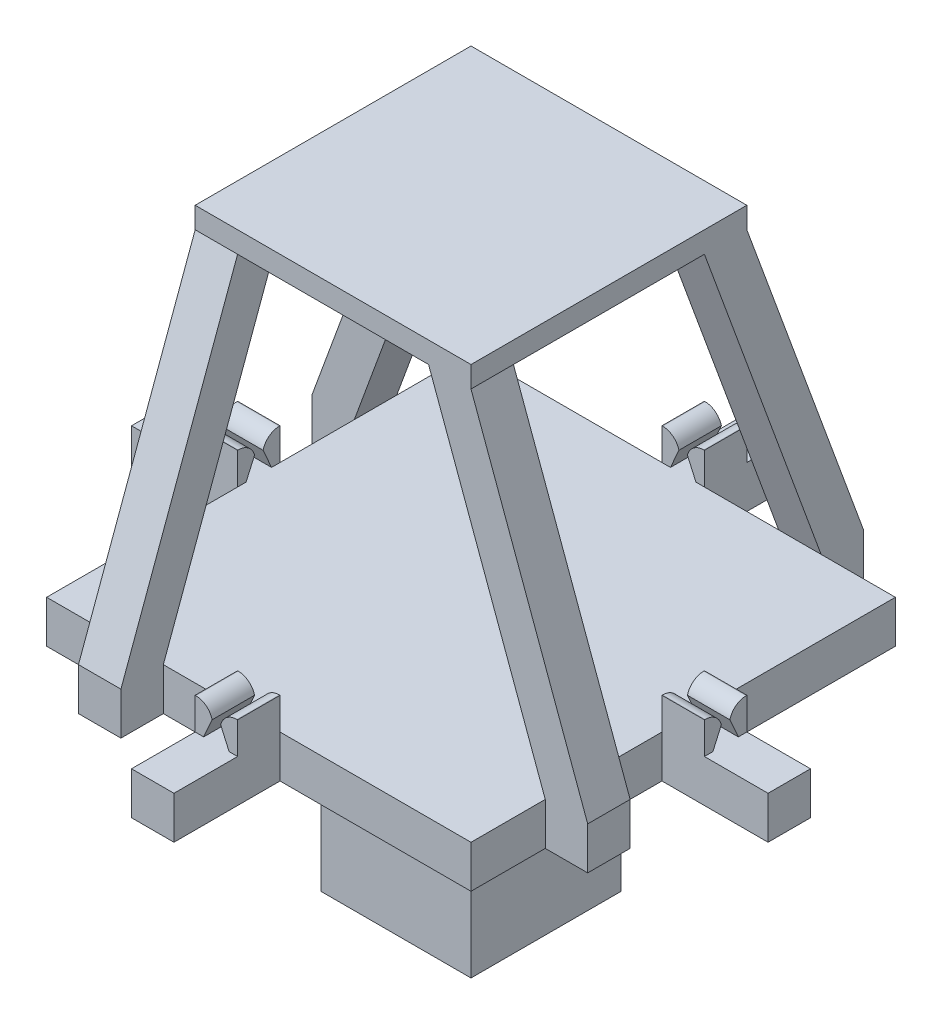
SolidWorks part; units mm, degrees
ref_plane "Front Plane" through (0, 0, 0) normal (0, 0, 1) x (1, 0, 0)
ref_plane "Top Plane" through (0, 0, 0) normal (0, 1, 0) x (1, 0, 0)
ref_plane "Right Plane" through (0, 0, 0) normal (1, 0, 0) x (0, 0, -1)
sketch "Sketch2" plane through (0, 0, 0) normal (0, 1, 0) x (1, 0, 0)
  line L1 (-50, -50) -> (50, -50)
  line L2 (-50, -50) -> (-50, 50)
  line L3 (-50, 50) -> (50, 50)
  line L4 (50, -50) -> (50, 50)
  line L5 (-50, -50) -> (50, 50) construction
  line L6 (-50, 50) -> (50, -50) construction
  point P0 (0, 0)
extrude "Boss-Extrude1" add sketch "Sketch2" along normal blind 5
sketch "Sketch3" plane through (0, 0, 0) normal (0, -1, 0) x (1, 0, 0)
  line L1 (-50, -50) -> (50, -50)
  line L2 (-50, -50) -> (-50, 50)
  line L3 (-50, 50) -> (50, 50)
  line L4 (50, -50) -> (50, 50)
  line L5 (-50, -50) -> (50, 50) construction
  line L6 (-50, 50) -> (50, -50) construction
  point P0 (0, 0)
extrude "Boss-Extrude2" add sketch "Sketch3" along normal blind 5
sketch "Sketch8" plane through (0, -5, 0) normal (0, -1, 0) x (1, 0, 0)
  circle A0 centre (0, 0) radius 5
extrude "Boss-Extrude7" add sketch "Sketch8" along normal blind 30
sketch "Sketch9" plane through (0, -35, 0) normal (0, -1, 0) x (1, 0, 0)
  line L1 (-17.7, 17.7) -> (17.7, 17.7)
  line L2 (-17.7, 17.7) -> (-17.7, -17.7)
  line L3 (-17.7, -17.7) -> (17.7, -17.7)
  line L4 (17.7, 17.7) -> (17.7, -17.7)
  line L5 (-17.7, 17.7) -> (17.7, -17.7) construction
  line L6 (-17.7, -17.7) -> (17.7, 17.7) construction
  point P0 (0, 0)
extrude "Boss-Extrude8" add sketch "Sketch9" along normal blind 20
sketch "Sketch10" plane through (0, -55, 0) normal (0, -1, 0) x (1, 0, 0)
  line L1 (-12.7, 12.7) -> (12.7, 12.7)
  line L2 (-12.7, 12.7) -> (-12.7, -12.7)
  line L3 (-12.7, -12.7) -> (12.7, -12.7)
  line L4 (12.7, 12.7) -> (12.7, -12.7)
  line L5 (-12.7, 12.7) -> (12.7, -12.7) construction
  line L6 (-12.7, -12.7) -> (12.7, 12.7) construction
  point P0 (0, 0)
extrude "Cut-Extrude1" cut sketch "Sketch10" against normal blind 12.7
sketch "Sketch11" plane through (50, 0, 0) normal (1, 0, 0) x (0, 0, -1)
  line L0 (5, -5) -> (5, 12.5)
  line L3 (-5, -5) -> (5, -5)
  line L5 (5, 12.5) -> (1, 12.5)
  line L6 (1, 12.5) -> (1, 9.5)
  line L7 (-5, -5) -> (-5, 12.5)
  line L8 (-5, 12.5) -> (-1, 12.5)
  line L9 (-1, 12.5) -> (-1, 9.5)
  line L10 (-50, 5) -> (50, 5) construction
  line L11 (-1, 9.5) -> (-3, 5)
  line L12 (-3, 5) -> (3, 5)
  line L13 (3, 5) -> (1, 9.5)
  point P0 (0, 0)
  point P8 (3, 5)
  point P12 (-3, 5)
extrude "Boss-Extrude21" add sketch "Sketch11" along normal blind 10
fillet "Fillet14" radius 4 1 edges at (55, 12.5, -1)
fillet "Fillet13" radius 4 1 edges at (55, 12.5, 1)
sketch "Sketch24" plane through (60, 0, 0) normal (1, 0, 0) x (0, 0, -1)
  line L1 (-5, 5) -> (5, 5)
  line L2 (-5, 5) -> (-5, -5)
  line L3 (-5, -5) -> (5, -5)
  line L4 (5, 5) -> (5, -5)
  line L5 (-5, 5) -> (5, -5) construction
  line L6 (-5, -5) -> (5, 5) construction
  point P0 (0, 0)
extrude "Boss-Extrude22" add sketch "Sketch24" along normal blind 15
sketch "Sketch13" plane through (-50, 0, 0) normal (-1, 0, 0) x (0, 0, 1)
  line L0 (50, -5) -> (-50, -5) construction
  line L2 (-5, 12.5) -> (-5, -5)
  line L3 (-5, -5) -> (5, -5)
  line L4 (5, 12.5) -> (5, -5)
  line L5 (5, 12.5) -> (1, 12.5)
  line L6 (1, 12.5) -> (1, 9.5)
  line L7 (-5, 12.5) -> (-1, 12.5)
  line L8 (-1, 12.5) -> (-1, 9.5)
  line L9 (-1, 9.5) -> (-3, 5)
  line L10 (-3, 5) -> (3, 5)
  line L11 (3, 5) -> (1, 9.5)
  point P0 (0, 0)
  point P8 (-3, 5)
  point P13 (3, 5)
extrude "Boss-Extrude25" add sketch "Sketch13" along normal blind 10
sketch "Sketch26" plane through (-60, 0, 0) normal (-1, 0, 0) x (0, 0, 1)
  line L0 (-5, -5) -> (5, -5) construction
  line L1 (-5, 5) -> (5, 5)
  line L2 (-5, 5) -> (-5, -5)
  line L3 (-5, -5) -> (5, -5)
  line L4 (5, 5) -> (5, -5)
  line L5 (-5, 5) -> (5, -5) construction
  line L6 (-5, -5) -> (5, 5) construction
  line L7 (-5, -5) -> (5, -5) construction
  point P0 (0, 0)
extrude "Boss-Extrude26" add sketch "Sketch26" along normal blind 15
fillet "Fillet18" radius 4 1 edges at (-55, 12.5, 1)
fillet "Fillet17" radius 4 1 edges at (-55, 12.5, -1)
sketch "Sketch14" plane through (0, 0, -50) normal (0, 0, -1) x (-1, 0, 0)
  line L0 (-5, 12.5) -> (-1, 12.5)
  line L2 (-5, 12.5) -> (-5, -5)
  line L3 (-5, -5) -> (5, -5)
  line L4 (5, 12.5) -> (5, -5)
  line L5 (5, 12.5) -> (1, 12.5)
  line L6 (-1, 12.5) -> (-1, 9.5)
  line L7 (1, 12.5) -> (1, 9.5)
  line L8 (-50, 5) -> (50, 5) construction
  line L9 (-1, 9.5) -> (-3, 5)
  line L10 (-3, 5) -> (3, 5)
  line L11 (3, 5) -> (1, 9.5)
  point P0 (0, 0)
  point P11 (3, 5)
  point P12 (-3, 5)
extrude "Boss-Extrude23" add sketch "Sketch14" along normal blind 10
sketch "Sketch25" plane through (0, 0, -60) normal (0, 0, -1) x (-1, 0, 0)
  line L1 (-5, 5) -> (5, 5)
  line L2 (-5, 5) -> (-5, -5)
  line L3 (-5, -5) -> (5, -5)
  line L4 (5, 5) -> (5, -5)
  line L5 (-5, 5) -> (5, -5) construction
  line L6 (-5, -5) -> (5, 5) construction
  point P0 (0, 0)
extrude "Boss-Extrude24" add sketch "Sketch25" along normal blind 15
fillet "Fillet15" radius 4 1 edges at (-1, 12.5, -55)
fillet "Fillet16" radius 4 1 edges at (1, 12.5, -55)
sketch "Sketch12" plane through (0, 0, 50) normal (0, 0, 1) x (1, 0, 0)
  line L0 (50, -5) -> (-50, -5) construction
  line L2 (-5, 12.5) -> (-5, -5)
  line L3 (-5, -5) -> (5, -5)
  line L4 (5, 12.5) -> (5, -5)
  line L5 (5, 12.5) -> (1, 12.5)
  line L6 (1, 12.5) -> (1, 9.5)
  line L7 (-5, -5) -> (5, -5) construction
  line L8 (-5, 12.5) -> (-1, 12.5)
  line L9 (-1, 12.5) -> (-1, 9.5)
  line L10 (-1, 9.5) -> (-3, 5)
  line L11 (-3, 5) -> (3, 5)
  line L12 (3, 5) -> (1, 9.5)
  point P0 (0, 0)
  point P10 (-3, 5)
  point P15 (3, 5)
extrude "Boss-Extrude10" add sketch "Sketch12" along normal blind 10
fillet "Fillet19" radius 4 1 edges at (-1, 12.5, 55)
sketch "Sketch27" plane through (0, 0, 60) normal (0, 0, 1) x (1, 0, 0)
  line L1 (-5, 5) -> (5, 5)
  line L2 (-5, 5) -> (-5, -5)
  line L3 (-5, -5) -> (5, -5)
  line L4 (5, 5) -> (5, -5)
  line L5 (-5, 5) -> (5, -5) construction
  line L6 (-5, -5) -> (5, 5) construction
  point P0 (0, 0)
extrude "Boss-Extrude27" add sketch "Sketch27" along normal blind 15
fillet "Fillet20" radius 4 1 edges at (1, 12.5, 55)
sketch "Sketch32" plane through (0, 0, 0) normal (0, 0, 1) x (1, 0, 0)
  point P0 (0, 85)
  point P1 (-22.5, 85)
  point P2 (22.5, 85)
ref_plane "Plane1" through (0, 85, 0) normal (0, 1, 0) x (1, 0, 0)
sketch "Sketch33" plane through (0, 85, 0) normal (0, 1, 0) x (1, 0, 0)
  line L6 (32.5, -32.5) -> (32.5, 32.5)
  line L7 (32.5, 32.5) -> (-32.5, 32.5)
  line L8 (-32.5, 32.5) -> (-32.5, -32.5)
  line L9 (-32.5, -32.5) -> (32.5, -32.5)
extrude "Boss-Extrude29" add sketch "Sketch33" against normal blind 5 separate body
sketch "Sketch30" plane through (-50, 0, 0) normal (-1, 0, 0) x (0, 0, 1)
  line L0 (-50, 5) -> (-5, 5) construction
  line L1 (5, 5) -> (50, 5) construction
  line L2 (-27.5, 5) -> (-22.5, 5)
  line L3 (-27.5, 5) -> (-32.5, 5)
  line L4 (-32.5, 5) -> (-32.5, -5)
  line L5 (-5, -5) -> (-50, -5) construction
  line L6 (-32.5, -5) -> (-22.5, -5)
  line L7 (-22.5, -5) -> (-22.5, 5)
  point P0 (-27.5, 5)
  point P1 (27.5, 5)
  point P4 (-27.5, 0)
  point P7 (27.5, 0)
  point P8 (-27.5, 0)
  point P9 (-27.5, 5)
extrude "Boss-Extrude28" add sketch "Sketch30" along normal blind 10
sketch "Sketch40" plane through (0, 0, -32.5) normal (0, 0, -1) x (-1, 0, 0)
  line L0 (60, 5) -> (32.5, 80)
  line L1 (32.5, 80) -> (22.5, 80)
  line L2 (22.5, 80) -> (50, 5)
  line L3 (50, 5) -> (60, 5)
extrude "Boss-Extrude32" add sketch "Sketch40" against normal blind 10
sketch "Sketch37" plane through (0, 0, 50) normal (0, 0, 1) x (1, 0, 0)
  line L0 (-50, 5) -> (-5, 5) construction
  line L1 (-27.5, 5) -> (-22.5, 5)
  line L2 (-27.5, 5) -> (-32.5, 5)
  line L3 (-32.5, 5) -> (-32.5, -5)
  line L4 (-5, -5) -> (-50, -5) construction
  line L5 (-32.5, -5) -> (-22.5, -5)
  line L6 (-22.5, -5) -> (-22.5, 5)
  point P0 (-27.5, 5)
extrude "Boss-Extrude31" add sketch "Sketch37" along normal blind 10
sketch "Sketch41" plane through (-32.5, 0, 0) normal (-1, 0, 0) x (0, 0, 1)
  line L0 (60, 5) -> (32.5, 80)
  line L1 (32.5, 80) -> (22.5, 80)
  line L2 (-22.5, 80) -> (32.5, 80) construction
  line L3 (22.5, 80) -> (50, 5)
  line L4 (50, 5) -> (60, 5)
extrude "Boss-Extrude33" add sketch "Sketch41" against normal blind 10
sketch "Sketch42" plane through (50, 0, 0) normal (1, 0, 0) x (0, 0, -1)
  line L0 (-50, 5) -> (-5, 5) construction
  line L1 (-27.5, 5) -> (-22.5, 5)
  line L2 (-27.5, 5) -> (-32.5, 5)
  line L3 (-32.5, 5) -> (-32.5, -5)
  line L4 (-5, -5) -> (-50, -5) construction
  line L5 (-32.5, -5) -> (-22.5, -5)
  line L6 (-22.5, -5) -> (-22.5, 5)
  point P0 (-27.5, 5)
extrude "Boss-Extrude34" add sketch "Sketch42" along normal blind 10
sketch "Sketch43" plane through (0, 0, 32.5) normal (0, 0, 1) x (1, 0, 0)
  line L0 (32.5, 80) -> (60, 5)
  line L1 (60, 5) -> (50, 5)
  line L2 (50, 5) -> (22.5, 80)
  line L3 (-22.5, 80) -> (32.5, 80) construction
  line L4 (22.5, 80) -> (32.5, 80)
extrude "Boss-Extrude35" add sketch "Sketch43" against normal blind 10
sketch "Sketch44" plane through (0, 0, -50) normal (0, 0, -1) x (-1, 0, 0)
  line L0 (-50, 5) -> (-5, 5) construction
  line L1 (-27.5, 5) -> (-22.5, 5)
  line L2 (-22.5, 5) -> (-22.5, -5)
  line L3 (-5, -5) -> (-50, -5) construction
  line L4 (-22.5, -5) -> (-32.5, -5)
  line L5 (-32.5, -5) -> (-32.5, 5)
  line L6 (-32.5, 5) -> (-27.5, 5)
  point P0 (-27.5, 5)
extrude "Boss-Extrude36" add sketch "Sketch44" along normal blind 10
sketch "Sketch45" plane through (32.5, 0, 0) normal (1, 0, 0) x (0, 0, -1)
  line L0 (32.5, 80) -> (60, 5)
  line L1 (60, 5) -> (50, 5)
  line L2 (50, 5) -> (22.5, 80)
  line L3 (22.5, 80) -> (32.5, 80)
extrude "Boss-Extrude37" add sketch "Sketch45" against normal blind 10
